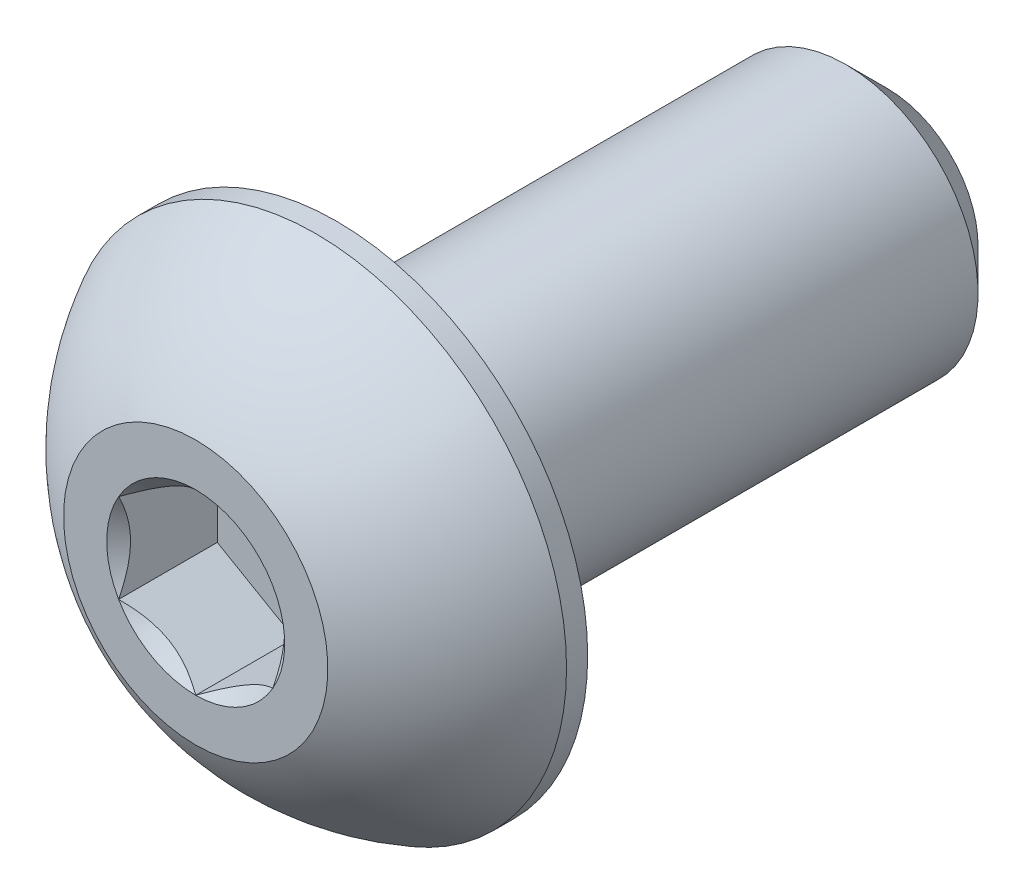
SolidWorks part; units mm, degrees
ref_plane "Front" through (0, 0, 0) normal (0, 0, 1) x (1, 0, 0)
ref_plane "Top" through (0, 0, 0) normal (0, 1, 0) x (1, 0, 0)
ref_plane "Right" through (0, 0, 0) normal (1, 0, 0) x (0, 0, -1)
sketch "Sketch1" plane through (0, 0, 0) normal (1, 0, 0) x (0, 0, -1)
  line L2 (0.8128, 0.762) -> (3.9878, 0.762)
  line L3 (3.9878, 0.762) -> (3.9878, 0)
  line L4 (3.9878, 0) -> (0.8128, 0)
  line L6 (0.6909, 1.4478) -> (0.8128, 1.4478) construction
  line L7 (3.9878, 0.762) -> (3.9878, -0.762) construction
  line L8 (0, 0) -> (0.8128, 0) construction
  line L9 (0.8128, 1.4478) -> (0.8128, -1.4478) construction
  line L11 (0.8128, 0.762) -> (0.8128, 0)
  line L13 (0, 0.4445) -> (0, -0.4445) construction
  line L14 (0, 0.4445) -> (0, 0.762) construction
  arc A3 (0, 0.762) -> (0.6909, 1.4478) centre (1.4422, 0) cw construction
  dimension "D1" = 0.1219
revolve "Revolve1" add sketch "Sketch1" angle 360 mid plane about L4
sketch "Sketch3" plane through (0, 0, -3.9878) normal (0, 0, -1) x (-1, 0, 0)
  circle A0 centre (0, 0) radius 0.762
curve "Helix/Spiral1" pitch 0.3175 height 5.08 turns 16
sketch "Sketch2" plane through (0, 0, 0) normal (1, 0, 0) x (0, 0, -1)
  line L0 (3.9878, 0.762) -> (4.2656, 0.762)
  line L1 (4.2656, 0.762) -> (4.1466, 0.5558)
  line L2 (4.1466, 0.5558) -> (4.1069, 0.5558)
  line L3 (4.1069, 0.5558) -> (3.9878, 0.762)
  line L4 (4.0473, 0.6589) -> (4.2061, 0.6589) construction
  dimension "D1" = 60
  dimension "D2" = 0.0397
  dimension "D3" = 0.1588
chamfer "Chamfer1" distance 0.2381 angle 45 1 edges at (0, 0.762, -3.9878)
sweep "Cut-Sweep1" [suppressed] cut profiles "Sketch2" path "Helix/Spiral1"
sketch "Sketch7" plane through (0, 0, 0) normal (1, 0, 0) x (0, 0, -1)
  line L6 (0.6909, 1.4478) -> (0.8128, 1.4478) construction
  line L8 (0, 0) -> (0.8128, 0) construction
  line L11 (0.8128, 1.4478) -> (0.8128, -1.4478) construction
  line L12 (0.6909, 1.4478) -> (0.8128, 1.4478)
  line L13 (0, 0) -> (0.8128, 0)
  line L14 (0, 0.4445) -> (0, -0.4445) construction
  line L15 (0.8128, 1.4478) -> (0.8128, 0)
  line L16 (0, 0.762) -> (0, 0)
  arc A2 (0.6909, 1.4478) -> (0, 0.762) centre (1.4422, 0) ccw construction
  arc A3 (0.6909, 1.4478) -> (0, 0.762) centre (1.4422, 0) ccw
revolve "Revolve2" add sketch "Sketch7" angle 360 mid plane about L13
sketch "Sketch5" plane through (0, 0, 0) normal (0, 0, 1) x (1, 0, 0)
  line L1 (0.4445, -0.2566) -> (0.4445, 0.2566)
  line L2 (0.4445, 0.2566) -> (0, 0.5133)
  line L3 (0, 0.5133) -> (-0.4445, 0.2566)
  line L4 (-0.4445, 0.2566) -> (-0.4445, -0.2566)
  line L5 (-0.4445, -0.2566) -> (0, -0.5133)
  line L6 (0, -0.5133) -> (0.4445, -0.2566)
  circle A0 centre (0, 0) radius 0.4445 construction
extrude "Cut-Extrude2" cut sketch "Sketch5" against normal blind 0.569
sketch "Sketch6" plane through (0, 0, 0) normal (0, 0, 1) x (1, 0, 0)
  circle A0 centre (0, 0) radius 0.5133
extrude "Cut-Extrude3" cut sketch "Sketch6" against normal blind 0.569 draft 45
sketch "Sketch9" [suppressed] plane through (0, 0, -8.2296) normal (0, 0, 1) x (1, 0, 0)
  circle A2 centre (0, 0) radius 7.9375
extrude "Boss-Extrude2" [suppressed] add sketch "Sketch9" against normal offset from surface (25.4 mm away) 22.225
sketch "Sketch10" plane through (0, 0, 0) normal (1, 0, 0) x (0, 0, -1)
  line L0 (3.9878, 0.762) -> (3.9878, -0.762) construction
  point P0 (3.5115, -0.762)
  dimension "D1" = 0.4763
equation "\"D2@Sketch2\" = \"D4@Helix/Spiral1\" * .125"
equation "\"D3@Sketch2\" = \"D4@Helix/Spiral1\" * .5"
equation "\"D1@Chamfer1\" = \"D4@Helix/Spiral1\" * .75"
equation "\"D1@Cut-Extrude2\" = \"Head Ht@Sketch1\" * .7"
equation "\"D1@Sketch1\" = \"Head Ht@Sketch1\" * .15"
equation "\"D1@Sketch10\" = \"D4@Helix/Spiral1\" * 1.5"
equation "\"D1@Cut-Extrude3\" = \"D1@Cut-Extrude2\""
